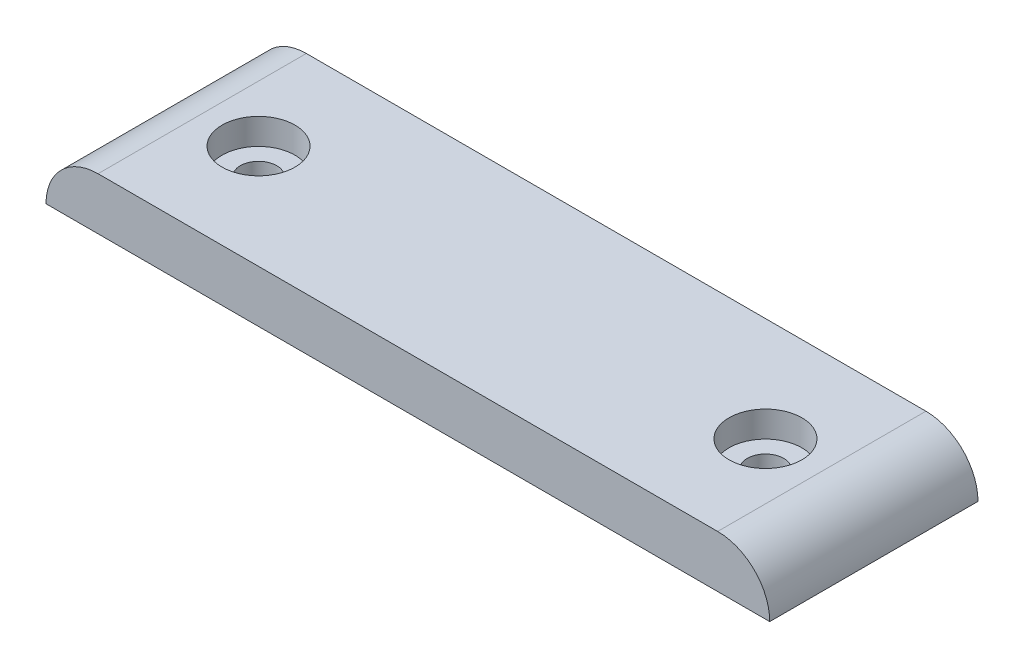
SolidWorks part; units mm, degrees
material "ABS"
ref_plane "Front Plane" through (0, 0, 0) normal (0, 0, 1) x (1, 0, 0)
ref_plane "Top Plane" through (0, 0, 0) normal (0, 1, 0) x (1, 0, 0)
ref_plane "Right Plane" through (0, 0, 0) normal (1, 0, 0) x (0, 0, -1)
sketch "Sketch1" plane through (0, 0, 0) normal (0, 1, 0) x (1, 0, 0)
  line L1 (-34.75, 10) -> (34.75, 10)
  line L2 (-34.75, 10) -> (-34.75, -10)
  line L3 (-34.75, -10) -> (34.75, -10)
  line L4 (34.75, 10) -> (34.75, -10)
  line L5 (-34.75, 10) -> (34.75, -10) construction
  line L6 (-34.75, -10) -> (34.75, 10) construction
  point P0 (0, 0)
  dimension "D1" = 20
  dimension "D2" = 69.5
extrude "Boss-Extrude1" add sketch "Sketch1" along normal blind 5
sketch "Sketch2" plane through (0, 5, 0) normal (0, 1, 0) x (1, 0, 0)
  line L0 (-34.75, -10) -> (34.75, -10) construction
  line L1 (-34.75, 10) -> (-20.45, 10) construction
  line L2 (-34.75, 10) -> (-34.75, -10) construction
  line L3 (-34.75, -10) -> (-20.45, -10) construction
  line L4 (-20.45, 10) -> (-20.45, -10) construction
  line L5 (0, 10) -> (0, -10) construction
  line L6 (34.75, 10) -> (-34.75, 10) construction
  line L7 (-27.6, 10) -> (-27.6, -10) construction
  line L8 (-27.6, 0) -> (-20.45, 0) construction
  circle A0 centre (-24.34, 0) radius 1.75
  circle A1 centre (24.34, 0) radius 1.75
  dimension "D3" = 3.5
  dimension "D1" = 14.3
  dimension "D2" = 3.89
extrude "Cut-Extrude2" cut sketch "Sketch2" against normal through all
sketch "Sketch3" plane through (0, 5, 0) normal (0, 1, 0) x (1, 0, 0)
  circle A0 centre (-24.34, 0) radius 3.5
  circle A1 centre (24.34, 0) radius 3.5
  dimension "D1" = 7
  dimension "D2" = 7
extrude "Cut-Extrude3" cut sketch "Sketch3" against normal blind 2.5
fillet "Fillet1" radius 5 2 edges at (34.75, 5, 0) (-34.75, 5, 0)
